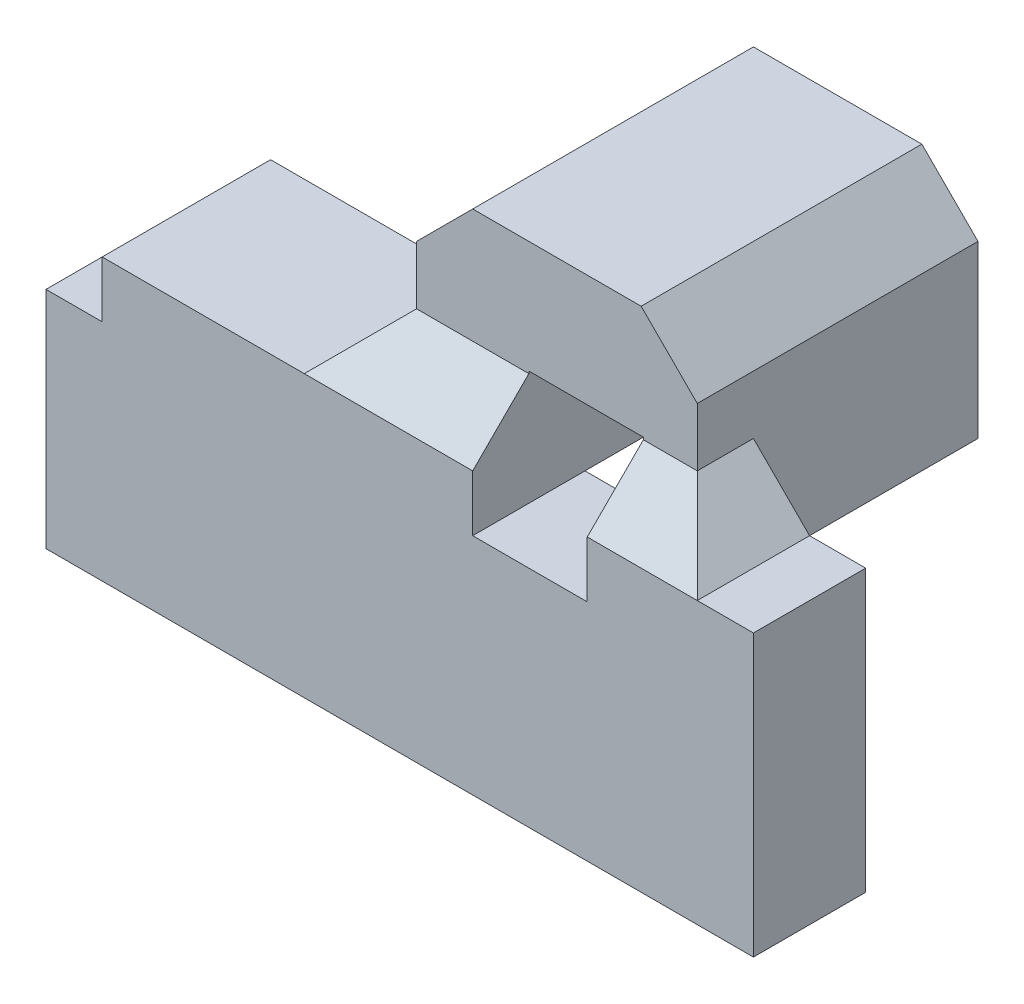
SolidWorks part; units mm, degrees
note: The reader was unsure of these and kept them because the rebuilt part matched: shared geometry of "Szkic5<3>".
material "ABS"
ref_plane "Płaszczyzna przednia" through (0, 0, 0) normal (0, 0, 1) x (1, 0, 0)
ref_plane "Płaszczyzna górna" through (0, 0, 0) normal (0, 1, 0) x (1, 0, 0)
ref_plane "Płaszczyzna prawa" through (0, 0, 0) normal (1, 0, 0) x (0, 0, -1)
sketch "Szkic1" plane through (0, 0, 0) normal (0, 0, 1) x (1, 0, 0)
  line L1 (-29, -10) -> (29, -10)
  line L2 (-29, -10) -> (-29, 10)
  line L3 (-29, 10) -> (29, 10)
  line L4 (29, -10) -> (29, 10)
  line L5 (-29, -10) -> (29, 10) construction
  line L6 (-29, 10) -> (29, -10) construction
  point P0 (0, 0)
  dimension "D1" = 20
  dimension "D2" = 58
extrude "Dodanie-wyciągnięcie1" add sketch "Szkic1" along normal blind 5
sketch "Szkic2" plane through (29, 0, 0) normal (1, 0, 0) x (0, 0, -1)
  line L0 (0, 15) -> (-10, 15)
  line L1 (0, 10) -> (5, 10)
  line L2 (0, 10) -> (0, 15)
  line L3 (0, 15) -> (5, 15)
  line L4 (5, 10) -> (5, 15)
  line L5 (-5, 10) -> (0, 10)
  line L6 (-10, 15) -> (-10, 10)
  line L7 (-10, 10) -> (-5, 10)
  dimension "D1" = 5
  dimension "D2" = 5
extrude "Dodanie-wyciągnięcie2" add sketch "Szkic2" against normal up to surface (58 mm away) up to face at (-29, 0, 2.5)
sketch "Szkic3" plane through (0, -10, 0) normal (0, -1, 0) x (1, 0, 0)
  line L0 (-29, 0) -> (-34, 5)
  line L1 (-29, 5) -> (-29, 0) construction
  line L2 (-29, 0) -> (-34, 0) construction
  line L3 (-34, 5) -> (-34, 10)
  line L4 (-34, 10) -> (-29, 10)
  line L5 (-29, 10) -> (-24, 5)
  line L6 (-29, 5) -> (29, 5) construction
  line L7 (-29, 5) -> (29, 5)
  line L8 (-29, 5) -> (-29, 0)
  line M7 (29, 5) -> (-29, 5)
  line M8 (-29, 5) -> (-29, 0)
  dimension "D1" = 45
  dimension "D2" = 5
  dimension "D3" = 5
extrude "Dodanie-wyciągnięcie3" add sketch "Szkic3" against normal blind 20 contours L5 L4 L3 L0 M8 M7
sketch "Szkic5" plane through (0, 0, 5) normal (0, 0, 1) x (1, 0, 0)
  line L0 (-34, 10) -> (-34, -10) construction
  line L1 (14.2, 10) -> (4, 10)
  line L2 (14.2, 10) -> (14.2, 20.2)
  line L3 (14.2, 20.2) -> (4, 20.2)
  line L4 (4, 10) -> (4, 20.2)
  line L5 (14.2, 10) -> (4, 20.2) construction
  line L6 (14.2, 20.2) -> (4, 10) construction
  line L7 (29, 10) -> (-24, 10) construction
  line L8 (29, 10) -> (-24, 10) construction
  line L10 (-6, 10) -> (19, 10)
  line L11 (-6, 10) -> (-6, 30.2)
  line L12 (-6, 30.2) -> (19, 30.2)
  line L13 (19, 10) -> (19, 30.2)
  point P0 (9.1, 15.1)
  point P9 (0, 0)
  dimension "D1" = 10.2
  dimension "D2" = 38
  dimension "D3" = 10
  dimension "D4" = 10
  dimension "D5" = 4.8
extrude "Dodanie-wyciągnięcie4" add sketch "Szkic5" against normal blind 10
extrude "Wytnij-wyciągnięcie2" cut sketch "Szkic5<3>" against normal through all and the other way through all
sketch "Szkic5<3>" plane through (0, 0, 5) normal (0, 0, 1) x (1, 0, 0) same geometry as "Szkic5"
sketch "Szkic6" plane through (0, 10, 0) normal (0, 1, 0) x (1, 0, 0)
  line L1 (-29, -10) -> (29, -10)
  line L2 (-29, -10) -> (-29, -5)
  line L3 (-29, -5) -> (29, -5)
  line L4 (29, -10) -> (29, -5)
  line L5 (29, -5) -> (14.2, -5) construction
  point P4 (0, 0)
  point P5 (0, 0)
  point P6 (0, 0)
  dimension "D1" = 5
  dimension "D2" = 58
extrude "Dodanie-wyciągnięcie5" add sketch "Szkic6" against normal blind 20
sketch "Szkic7" plane through (0, -10, 0) normal (0, -1, 0) x (1, 0, 0)
  line L0 (-34, 10) -> (29, 10) construction
  line L1 (-34, 5) -> (-34, 10) construction
  circle A0 centre (-19, 5) radius 2
  circle A1 centre (11, 5) radius 2
  dimension "D1" = 4
  dimension "D2" = 5
  dimension "D3" = 15
  dimension "D4" = 30
extrude "Wytnij-wyciągnięcie3" cut sketch "Szkic7" against normal blind 10
sketch "Szkic10" plane through (0, 0, -5) normal (0, 0, -1) x (-1, 0, 0)
  line L0 (6, 15) -> (6, 10)
  line L10 (-4, 20.2) -> (-4, 10)
  line L11 (-4, 10) -> (29, 10)
  line L12 (29, 10) -> (29, 15)
  line L13 (29, 15) -> (6, 15)
  line L14 (6, 15) -> (6, 30.2)
  line L15 (6, 30.2) -> (-19, 30.2)
  line L16 (-19, 30.2) -> (-19, 15)
  line L17 (-29, 10) -> (-14.2, 10)
  line L18 (-14.2, 10) -> (-14.2, 20.2)
  line L19 (-14.2, 20.2) -> (-4, 20.2)
  line L20 (-4, 20.2) -> (-4, 10)
  line L21 (-4, 10) -> (29, 10)
  line L22 (29, 10) -> (29, 15)
  line L23 (29, 15) -> (6, 15)
  line L24 (6, 15) -> (6, 30.2)
  line L25 (6, 30.2) -> (-19, 30.2)
  line L26 (-19, 30.2) -> (-19, 15)
  line L27 (-29, 10) -> (-14.2, 10)
  line L28 (-14.2, 10) -> (-14.2, 20.2)
  line L29 (-14.2, 20.2) -> (-4, 20.2)
  line L33 (-19, 15) -> (-29, 15)
  line L34 (-19, 15) -> (-29, 15)
  line L35 (-29, 15) -> (-29, 10)
  line L36 (-29, 15) -> (-29, 10)
  line M11 (-4, 20.2) -> (-4, 10)
  line M12 (-4, 10) -> (29, 10)
  line M15 (6, 15) -> (6, 30.2)
  line M16 (6, 30.2) -> (-19, 30.2)
  line M17 (-19, 30.2) -> (-19, 15)
  line M18 (-29, 10) -> (-14.2, 10)
  line M19 (-14.2, 10) -> (-14.2, 20.2)
  line M20 (-14.2, 20.2) -> (-4, 20.2)
  dimension "D1" = 0
extrude "Dodanie-wyciągnięcie8" add sketch "Szkic10" along normal blind 10 contours L0 M15 M16 M17 M18 M19 M20 M11 M12
sketch "Szkic11" plane through (0, 0, -15) normal (0, 0, -1) x (-1, 0, 0)
  line L0 (-14.2, 10) -> (-4, 10)
  line L8 (6, 10) -> (6, 30.2)
  line L9 (6, 30.2) -> (-19, 30.2)
  line L10 (-19, 30.2) -> (-19, 15)
  line L11 (-29, 10) -> (-14.2, 10)
  line L12 (-14.2, 10) -> (-14.2, 20.2)
  line L13 (-14.2, 20.2) -> (-4, 20.2)
  line L14 (-4, 20.2) -> (-4, 10)
  line L15 (-4, 10) -> (6, 10)
  line L16 (6, 10) -> (6, 30.2)
  line L17 (6, 30.2) -> (-19, 30.2)
  line L18 (-19, 30.2) -> (-19, 15)
  line L19 (-29, 10) -> (-14.2, 10)
  line L20 (-14.2, 10) -> (-14.2, 20.2)
  line L21 (-14.2, 20.2) -> (-4, 20.2)
  line L22 (-4, 20.2) -> (-4, 10)
  line L23 (-4, 10) -> (6, 10)
  line L27 (-19, 15) -> (-29, 15)
  line L28 (-19, 15) -> (-29, 15)
  line L29 (-29, 15) -> (-29, 10)
  line L30 (-29, 15) -> (-29, 10)
  line M9 (6, 10) -> (6, 30.2)
  line M10 (6, 30.2) -> (-19, 30.2)
  line M11 (-19, 30.2) -> (-19, 15)
  line M12 (-29, 10) -> (-14.2, 10)
  line M13 (-14.2, 10) -> (-14.2, 20.2)
  line M14 (-14.2, 20.2) -> (-4, 20.2)
  line M15 (-4, 20.2) -> (-4, 10)
  line M16 (-4, 10) -> (6, 10)
  dimension "D1" = 0
extrude "Dodanie-wyciągnięcie9" add sketch "Szkic11" along normal blind 5 contours M16 M9 M10 M11 M12 M13 M14 M15 | L0 M13 M15 M14
chamfer "Sfazowanie2" distance 5 angle 45 2 edges at (19, 30.2, -7.5) (-6, 30.2, -7.5)
chamfer "Sfazowanie3" distance 5 angle 45 6 edges at (14.2, 15, 7.5) (4, 15, 7.5) (16.6, 15, 5) (-1, 15, 5) (-6, 15, 0) (19, 15, -7.5)
sketch "Szkic12" plane through (0, 10, 0) normal (0, -1, 0) x (1, 0, 0)
  line L0 (19, 10) -> (19, -20) construction
  line L1 (29, 0) -> (14.2, 0) construction
  line L2 (19, 10) -> (19, -20)
  line L3 (29, 0) -> (14.2, 0)
  line L4 (29, -20) -> (-6, -20) construction
  line L5 (29, 0) -> (29, -20) construction
  line L6 (29, -20) -> (-6, -20)
  line L7 (29, 0) -> (29, -20)
  line M8 (-6, -20) -> (29, -20)
  line M9 (29, -20) -> (29, 0)
  line M10 (29, 0) -> (14.2, 0)
extrude "Wytnij-wyciągnięcie4" cut sketch "Szkic12" against normal blind 10 contours L2 M10 M8 M9
